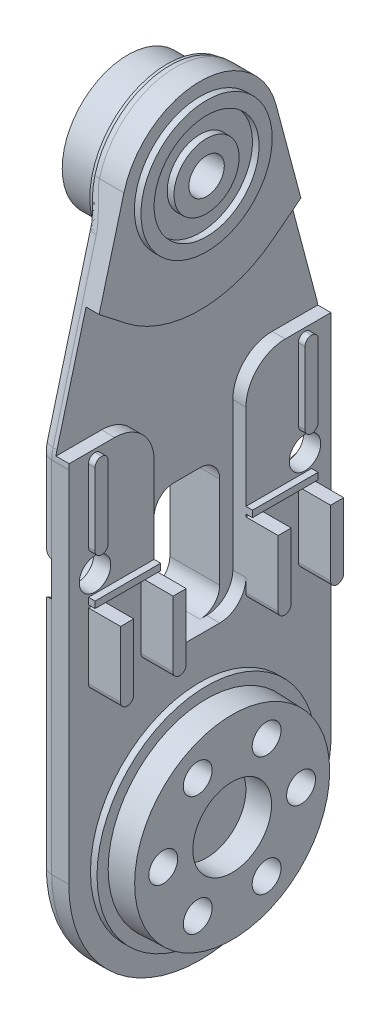
SolidWorks part; units mm, degrees
ref_plane "前视基准面" through (0, 0, 0) normal (0, 0, 1) x (1, 0, 0)
ref_plane "上视基准面" through (0, 0, 0) normal (0, 1, 0) x (1, 0, 0)
ref_plane "右视基准面" through (0, 0, 0) normal (1, 0, 0) x (0, 0, -1)
sketch "草图2" plane through (0, 0, 0) normal (1, 0, 0) x (0, 0, -1)
  line L0 (-5.7983, 15.7927) -> (-10, 0)
  line L1 (-10, 0) -> (0, 0) construction
  line L2 (-10, 0) -> (-10, -27.75)
  line L3 (-10, -27.75) -> (10, -27.75) construction
  line L4 (10, 0) -> (10, -27.75)
  line L5 (5.7983, 15.7927) -> (10, 0)
  line L6 (0, 14.25) -> (0, -27.75) construction
  line L7 (0, 0) -> (10, 0) construction
  arc A0 (5.7983, 15.7927) -> (-5.7983, 15.7927) centre (0, 14.25) ccw
  arc A1 (-10, -27.75) -> (10, -27.75) centre (0, -27.75) ccw
  arc A2 (10, -27.75) -> (0, -17.75) centre (0, -27.75) ccw construction
  arc A3 (0, -17.75) -> (-10, -27.75) centre (0, -27.75) ccw construction
  arc A4 (-5.7983, 15.7927) -> (0, 8.25) centre (0, 14.25) ccw construction
  arc A5 (0, 8.25) -> (5.7983, 15.7927) centre (0, 14.25) ccw construction
  dimension "D1" = 12
  dimension "D3" = 20
  dimension "D2" = 14.25
  dimension "D4" = 42
extrude "凸台-拉伸1" add sketch "草图2" against normal blind 1.3
ref_axis "基准轴1" through (-1.3, 14.25, 0) along (1, 0, 0)
ref_axis "基准轴2" through (-1.3, -27.75, 0) along (1, 0, 0)
sketch "草图3" plane through (0, 0, 0) normal (1, 0, 0) x (0, 0, -1)
  line L0 (-7.6853, 8.7) -> (-5.5889, 7.0685)
  line L1 (7.6853, 8.7) -> (5.5889, 7.0685)
  line L2 (10, 0) -> (5.7983, 15.7927) construction
  line L3 (0, 14.25) -> (0, 0) construction
  line L4 (-5.7983, 15.7927) -> (-7.6853, 8.7)
  line L5 (5.7983, 15.7927) -> (7.6853, 8.7)
  line L6 (-5.7983, 15.7927) -> (-10, 0) construction
  arc A0 (-5.5889, 7.0685) -> (5.5889, 7.0685) centre (0, 14.25) ccw
  arc A1 (5.7983, 15.7927) -> (-5.7983, 15.7927) centre (0, 14.25) ccw
  arc A2 (7.5574, 9.1809) -> (-7.5574, 9.1809) centre (0, 14.25) ccw construction
  arc A3 (-5.7983, 15.7927) -> (0, 8.25) centre (0, 14.25) ccw construction
  arc A4 (0, 8.25) -> (5.7983, 15.7927) centre (0, 14.25) ccw construction
  arc A5 (5.5889, 7.0685) -> (7.5574, 9.1809) centre (0, 14.25) ccw construction
  arc A6 (-7.5574, 9.1809) -> (-5.5889, 7.0685) centre (0, 14.25) ccw construction
  dimension "D1" = 18.2
  dimension "D3" = 12
  dimension "D2" = 5.55
extrude "凸台-拉伸2" add sketch "草图3" along normal blind 1
sketch "草图4" plane through (1, 0, 0) normal (1, 0, 0) x (0, 0, -1)
  circle A0 centre (0, 14.25) radius 5
  circle A1 centre (0, 14.25) radius 4
  dimension "D1" = 10
  dimension "D2" = 8
extrude "凸台-拉伸3" add sketch "草图4" along normal blind 0.5
sketch "草图5" plane through (1, 0, 0) normal (1, 0, 0) x (0, 0, -1)
  circle A0 centre (0, 14.25) radius 2.5
  circle A1 centre (0, 14.25) radius 1.375
  dimension "D1" = 5
  dimension "D2" = 2.75
extrude "凸台-拉伸4" add sketch "草图5" along normal up to surface (0.5 mm away) draft 2 contours A0 up to face at (1.5, 14.25, -5)
sketch "草图6" plane through (-1.3, 0, 0) normal (-1, 0, 0) x (0, 0, 1)
  circle A0 centre (0, 14.25) radius 5.9
  dimension "D1" = 11.8
extrude "凸台-拉伸5" add sketch "草图6" along normal blind 0.2
sketch "草图7" plane through (-1.5, 0, 0) normal (-1, 0, 0) x (0, 0, 1)
  circle A0 centre (0, 14.25) radius 5
  dimension "D1" = 10
extrude "凸台-拉伸6" add sketch "草图7" along normal blind 3
hole_wizard "M2 六角圆柱头螺钉的柱形沉头孔1" positions "草图8" profile "草图10" counterbore size "M2" standard "GB" end condition through all
sketch "草图8" plane through (-4.5, 0, 0) normal (-1, 0, 0) x (0, 0, 1)
  point P0 (0, 14.25)
sketch "草图10" plane through (-4.5, 14.25, 0) normal (0, 1, 0) x (0, 0, 1)
  line L0 (0, 0) -> (0, 6)
  line L1 (0, 6) -> (1.35, 6)
  line L3 (1.35, 6) -> (1.35, 3.5)
  line L4 (1.35, 3.5) -> (2.75, 3.5)
  line L5 (2.75, 3.5) -> (2.75, 0)
  line L7 (2.75, 0) -> (0, 0)
  line L11 (0, -6.35) -> (0, 107.95) construction
  dimension "通孔孔直径" = 2.7
  dimension "通孔孔深度" = 6
  dimension "柱形沉头孔直径" = 5.5
  dimension "柱形沉头孔深度" = 3.5
sketch "草图11" plane through (0, 0, 0) normal (1, 0, 0) x (0, 0, -1)
  line L0 (-10, 0) -> (-3.5, 0)
  line L1 (-3.5, 0) -> (3.5, 0) construction
  line L2 (-3.5, 0) -> (3.5, 0) construction
  line L3 (-3.5, 0) -> (-3.5, -14.25)
  line L4 (-1.5, -16.25) -> (1.5, -16.25)
  line L5 (3.5, 0) -> (3.5, -14.25)
  line L6 (7.6853, 8.7) -> (5.5889, 7.0685)
  line L7 (-5.5889, 7.0685) -> (-7.6853, 8.7)
  line L8 (-7.6853, 8.7) -> (-10, 0)
  line L9 (-10, 0) -> (-10, -27.75)
  line L10 (10, -27.75) -> (10, 0)
  line L11 (10, 0) -> (7.6853, 8.7)
  line L15 (-10, 0) -> (-10, -27.75)
  line L16 (10, -27.75) -> (10, 0)
  line L18 (3.5, 0) -> (10, 0)
  arc A0 (1.5, -16.25) -> (3.5, -14.25) centre (1.5, -14.25) ccw
  arc A1 (-1.5, -16.25) -> (-3.5, -14.25) centre (-1.5, -14.25) cw
  arc A2 (-5.5889, 7.0685) -> (5.5889, 7.0685) centre (0, 14.25) ccw
  arc A3 (-10, -27.75) -> (10, -27.75) centre (0, -27.75) ccw
  arc A5 (-10, -27.75) -> (10, -27.75) centre (0, -27.75) ccw
  point P18 (3.5, -16.25)
  point P22 (-3.5, -16.25)
  dimension "D4" = 2
  dimension "D2" = 7
  dimension "D3" = 16.25
  dimension "D1" = 0
extrude "凸台-拉伸7" add sketch "草图11" along normal blind 1
sketch "草图12" plane through (1, 0, 0) normal (1, 0, 0) x (0, 0, -1)
  circle A0 centre (0, -27.75) radius 8.35
  dimension "D1" = 16.7
extrude "凸台-拉伸8" add sketch "草图12" along normal blind 0.5
sketch "草图13" plane through (1.5, 0, 0) normal (1, 0, 0) x (0, 0, -1)
  circle A0 centre (0, -27.75) radius 7.5
  dimension "D1" = 15
extrude "凸台-拉伸9" add sketch "草图13" along normal blind 1.95 draft 2
sketch "草图16" plane through (3.45, 0, 0) normal (1, 0, 0) x (0, 0, -1)
  circle A0 centre (0, -27.75) radius 3
  dimension "D1" = 6
extrude "切除-拉伸1" cut sketch "草图16" against normal blind 1.95
sketch "草图17" plane through (1, 0, 0) normal (1, 0, 0) x (0, 0, -1)
  line L0 (-3.5, 0) -> (-10, 0) construction
  line L1 (-7.5, -6.75) -> (-8.5, -6.75)
  line L2 (-7.5, -6.75) -> (-7.5, -0.25)
  line L3 (-7.5, -0.25) -> (-8.5, -0.25)
  line L4 (-8.5, -6.75) -> (-8.5, -0.25)
  line L5 (-3.5, -14.25) -> (-3.5, 0) construction
  line L6 (-3.5, -10.05) -> (-8.5, -10.05)
  line L7 (-3.5, -10.05) -> (-3.5, -9.55)
  line L8 (-3.5, -9.55) -> (-8.5, -9.55)
  line L9 (-8.5, -10.05) -> (-8.5, -9.55)
  line L11 (-4.5, -10.25) -> (-3.5, -10.25)
  line L12 (-4.5, -10.25) -> (-4.5, -15.75)
  line L13 (-4.5, -15.75) -> (-3.5, -15.75)
  line L14 (-3.5, -10.25) -> (-3.5, -15.75)
  line L15 (-8.5, -10.25) -> (-7.5, -10.25)
  line L16 (-8.5, -10.25) -> (-8.5, -15.75)
  line L17 (-8.5, -15.75) -> (-7.5, -15.75)
  line L18 (-7.5, -10.25) -> (-7.5, -15.75)
  line M21 (-3.5, -14.25) -> (-3.5, 0)
  dimension "D1" = 0.25
  dimension "D2" = 1
  dimension "D3" = 7.5
  dimension "D4" = 6.5
  dimension "D5" = 5.5
  dimension "D6" = 0.2
  dimension "D7" = 0.5
  dimension "D8" = 5
  dimension "D9" = 9.55
  dimension "D10" = 1
  dimension "D11" = 3
extrude "凸台-拉伸10" add sketch "草图17" along normal blind 0.5 contours L4 L1 L2 L3 | L9 L6 L8 M21 region at (1, -3.5, 8) region at (1, -9.8, 6)
extrude "凸台-拉伸11" add sketch "草图17<3>" along normal blind 2.45 contours L12 L13 L11 M21 | L18 L15 L16 L17 region at (1, -13, 4) region at (1, -13, 8)
sketch "草图17<3>" plane through (1, 0, 0) normal (1, 0, 0) x (0, 0, -1) same geometry as "草图17"
fillet "圆角1" radius 0.5 8 edges at (2.225, -15.75, 7.5) (2.225, -15.75, 3.5) (2.225, -15.75, 4.5) (2.225, -15.75, 8.5) (1.25, -6.75, 7.5) (1.25, -6.75, 8.5) (1.25, -0.25, 7.5) (1.25, -0.25, 8.5)
sketch "草图18" plane through (-1.3, 0, 0) normal (-1, 0, 0) x (0, 0, 1)
  line L0 (-10, -27.75) -> (-10, 0) construction
  line L1 (-10, 0) -> (-5.7983, 15.7927) construction
  circle A0 centre (-7, -0.3923) radius 3
  line M6 (-5.7983, 15.7927) -> (-10, 0)
  line M7 (-10, 0) -> (-10, -27.75)
  dimension "D1" = 6
extrude "切除-拉伸2" cut sketch "草图18" against normal through all contours A0 M6 M7 region at (-1.3, -0.0026, -9.9798)
mirror "镜向1" about plane through (0, 0, 0) normal (0, 0, 1) of "切除-拉伸2", "圆角1", "凸台-拉伸11", "凸台-拉伸10"
fillet "圆角2" radius 3 2 edges at (0.5, 0, 3.5) (0.5, 0, -3.5)
sketch "草图19" plane through (-1.3, 0, 0) normal (-1, 0, 0) x (0, 0, 1)
  line L0 (0, -2.35) -> (0, -27.75) construction
  line L1 (6, -2.35) -> (6, -27.75)
  line L2 (-6, -2.35) -> (-6, -27.75)
  arc A0 (6, -2.35) -> (-6, -2.35) centre (0, -2.35) ccw
  arc A1 (-6, -27.75) -> (6, -27.75) centre (0, -27.75) ccw
  point P2 (0, -15.05)
  dimension "D2" = 6
  dimension "D1" = 25.4
extrude "凸台-拉伸12" add sketch "草图19" along normal blind 2.5
fillet "圆角3" radius 0.9 4 edges at (-3.8, -15.05, -6) (-3.8, 3.65, 0) (-3.8, -15.05, 6) (-3.8, -33.75, 0)
fillet "圆角4" radius 2.4 4 edges at (-1.3, -15.05, -6) (-1.3, 3.65, 0) (-1.3, -15.05, 6) (-1.3, -33.75, 0)
hole_wizard "M2 六角圆柱头螺钉的柱形沉头孔2" positions "草图22" profile "草图23" counterbore size "M2" standard "GB" end condition through all
sketch "草图22" plane through (-3.8, 0, 0) normal (-1, 0, 0) x (0, 0, 1)
  line L0 (0, -27.75) -> (-5.25, -27.75)
  point P0 (-5.25, -27.75)
  dimension "D1" = 5.25
sketch "草图23" plane through (-3.8, -27.75, -5.25) normal (0, 1, 0) x (0, 0, 1)
  line L0 (0, 0) -> (0, 7.25)
  line L1 (0, 7.25) -> (1.1, 7.25)
  line L3 (1.1, 7.25) -> (1.1, 4.4)
  line L4 (1.1, 4.4) -> (2.25, 4.4)
  line L5 (2.25, 4.4) -> (2.25, 0)
  line L7 (2.25, 0) -> (0, 0)
  line L11 (0, -6.35) -> (0, 107.95) construction
  dimension "通孔孔直径" = 2.2
  dimension "通孔孔深度" = 7.25
  dimension "柱形沉头孔直径" = 4.5
  dimension "柱形沉头孔深度" = 4.4
pattern_circular "阵列(圆周)1" count 6 over 360 about axis through (-1.3, -27.75, 0) along (1, 0, 0) of "M2 六角圆柱头螺钉的柱形沉头孔2"
fillet "圆角5" radius 1 7 edges at (-1.3, -37.75, 0) (-1.3, -14.0711, 10) (-1.3, -0.0033, 9.9747) (-1.3, 8.0859, 7.8487) (-1.3, 8.0859, -7.8487) (-1.3, -0.0033, -9.9747) (-1.3, -14.0711, -10)
hole_wizard "M2 六角圆柱头螺钉的柱形沉头孔3" positions "草图24" profile "草图25" counterbore size "M2" standard "GB" end condition through all
sketch "草图24" plane through (-3.8, 0, 0) normal (-1, 0, 0) x (0, 0, 1)
  line L0 (-8, -8.25) -> (8, -8.25) construction
  line L2 (0, 0) -> (0, -8.25) construction
  point P0 (-8, -8.25)
  point P2 (8, -8.25)
  dimension "D1" = 8.25
  dimension "D2" = 16
sketch "草图25" plane through (-3.8, -8.25, -8) normal (0, 1, 0) x (0, 0, 1)
  line L0 (0, 0) -> (0, 7.25)
  line L1 (0, 7.25) -> (1.2, 7.25)
  line L3 (1.2, 7.25) -> (1.2, 3.5)
  line L4 (1.2, 3.5) -> (2.4, 3.5)
  line L5 (2.4, 3.5) -> (2.4, 0)
  line L7 (2.4, 0) -> (0, 0)
  line L11 (0, -6.35) -> (0, 107.95) construction
  dimension "通孔孔直径" = 2.4
  dimension "通孔孔深度" = 7.25
  dimension "柱形沉头孔直径" = 4.8
  dimension "柱形沉头孔深度" = 3.5
sketch "草图21" plane through (-3.8, 0, 0) normal (-1, 0, 0) x (0, 0, 1)
  line L0 (0, -16.25) -> (0, -27.75) construction
  line L1 (1, -16.25) -> (-1, -16.25)
  line L2 (2.5, -14.75) -> (2.5, -7.75)
  line L3 (1, -6.25) -> (-1, -6.25)
  line L4 (-2.5, -14.75) -> (-2.5, -7.75)
  arc A0 (2.5, -14.75) -> (1, -16.25) centre (1, -14.75) cw
  arc A1 (-1, -16.25) -> (-2.5, -14.75) centre (-1, -14.75) cw
  arc A2 (2.5, -7.75) -> (1, -6.25) centre (1, -7.75) ccw
  arc A3 (-2.5, -7.75) -> (-1, -6.25) centre (-1, -7.75) cw
  point P10 (2.5, -16.25)
  point P13 (-2.5, -16.25)
  point P16 (2.5, -6.25)
  dimension "D4" = 1.5
  dimension "D1" = 11.5
  dimension "D2" = 10
  dimension "D3" = 5
extrude "切除-拉伸3" cut sketch "草图21" against normal through all
